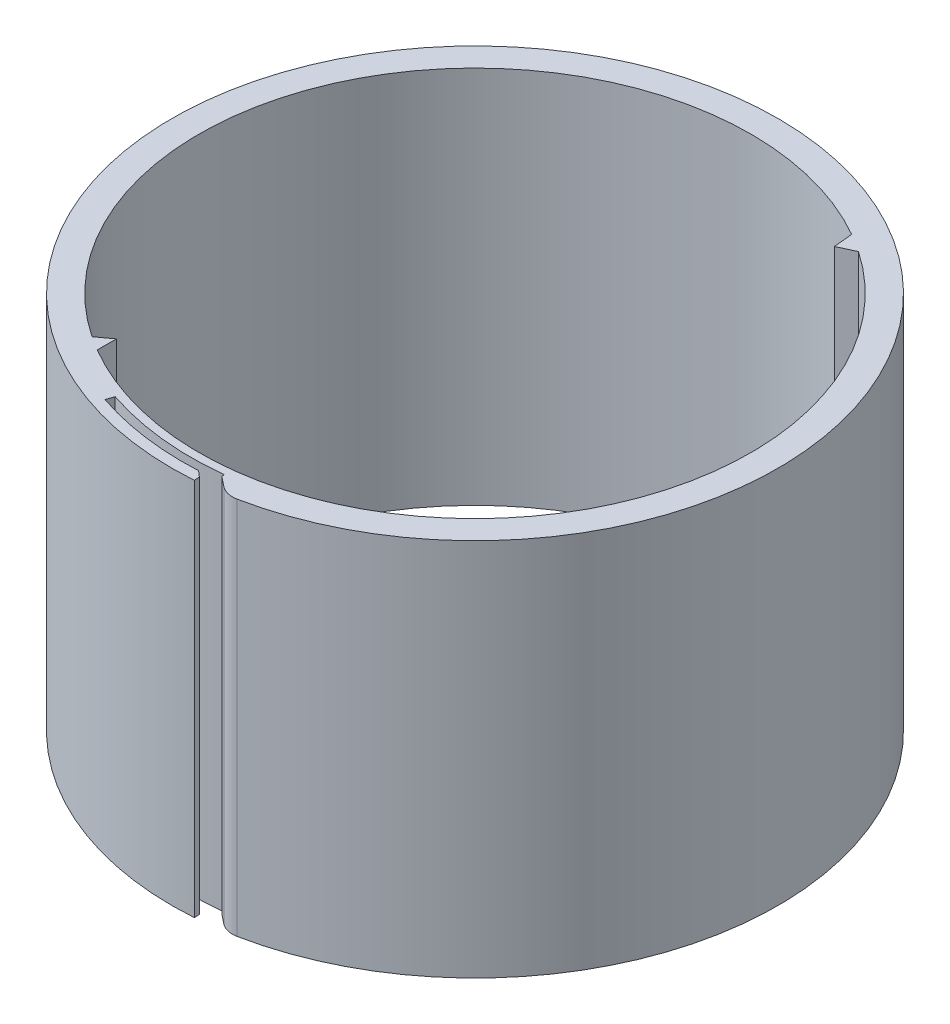
SolidWorks part; units mm, degrees
ref_plane "Спереди" through (0, 0, 0) normal (0, 0, 1) x (1, 0, 0)
ref_plane "Сверху" through (0, 0, 0) normal (0, 1, 0) x (1, 0, 0)
ref_plane "Справа" through (0, 0, 0) normal (1, 0, 0) x (0, 0, -1)
ref_plane "Плоскость4" through (0, 65.6673, 0) normal (0, -1, 0) x (-1, 0, 0)
sketch "Эскиз1" plane through (0, 65.6673, 0) normal (0, -1, 0) x (-1, 0, 0)
  line L0 (-43.837, -8.9443) -> (-42.3129, -9.6483)
  line L1 (-42.3129, -9.6483) -> (-42.1462, -7.8847)
  line L2 (-15.2363, -51.1695) -> (-16.5342, -50.2198)
  line L3 (-16.5342, -50.2198) -> (-16.5342, -51.9862)
  line L4 (-32.5696, -57.8315) -> (-32.376, -56.0996)
  line L6 (-21.1004, -54.8959) -> (-20.864, -55.6)
  line L8 (-31.3864, -56.9359) -> (-31.4578, -57.9334)
  circle A0 centre (-29.4597, -30.0048) radius 25.5
  arc A4 (-32.376, -56.0996) -> (-21.1004, -54.8959) centre (-29.4597, -30.0048) ccw
  arc A5 (-31.3864, -56.9359) -> (-20.864, -55.6) centre (-29.4597, -30.0048) ccw
  arc A6 (-32.5696, -57.8315) -> (-31.4578, -57.9334) centre (-29.4597, -30.0048) cw
extrude "Бобышка-Вытянуть1" add sketch "Эскиз1" along normal blind 35 contours L1 A0 L0 | A6 L4 A4 L6 A5 L8 A0 | L3 A0 L2 region at (42.7696, 65.6673, 8.8182) region at (16.0994, 65.6673, 51.1298) region at (26.9774, 65.6673, 2.9102)
chamfer "Фаска1" distance 1.5 angle 45 1 edges at (32.5696, 48.1673, 57.8315)
fillet "Скругление1" radius 2 1 edges at (34.0181, 48.1673, 57.6312)
chamfer "Фаска2" distance 0.5 angle 45 1 edges at (31.3864, 48.1673, 56.9359)
